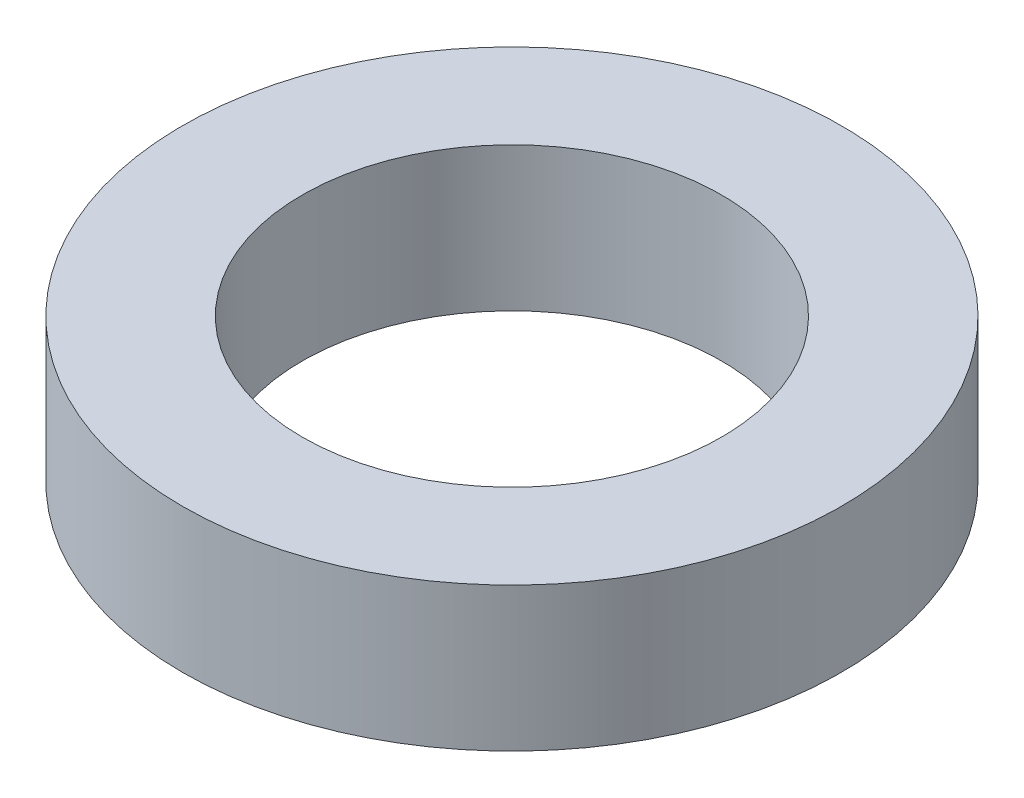
SolidWorks part; units mm, degrees
ref_plane "Front Plane" through (0, 0, 0) normal (0, 0, 1) x (1, 0, 0)
ref_plane "Top Plane" through (0, 0, 0) normal (0, 1, 0) x (1, 0, 0)
ref_plane "Right Plane" through (0, 0, 0) normal (1, 0, 0) x (0, 0, -1)
sketch "Sketch1" plane through (0, 0, 0) normal (0, 1, 0) x (1, 0, 0)
  circle A0 centre (0, 0) radius 27.5
  dimension "FLANGE_OD" = 55
extrude "Boss-Extrude1" add sketch "Sketch1" along normal blind 12
sketch "Sketch2" plane through (0, 0, 0) normal (0, 1, 0) x (1, 0, 0)
  circle A0 centre (0, 0) radius 17.5
  dimension "BORE_D" = 35
extrude "Cut-Extrude1" cut sketch "Sketch2" along normal through all
sketch "Sketch3" plane through (0, 12, 0) normal (0, 1, 0) x (1, 0, 0)
  circle A0 centre (0, 0) radius 10.1533 construction
  circle A1 centre (-10.1533, 0) radius 1.643
  dimension "BOLT_D" = 3.2859
  dimension "BOLT_PCD" = 20.3066
extrude "Cut-Extrude2" cut sketch "Sketch3" against normal blind 8.934 rebuild error yes
pattern_circular "CirPattern1" count 8 over 360 rebuild error yes
